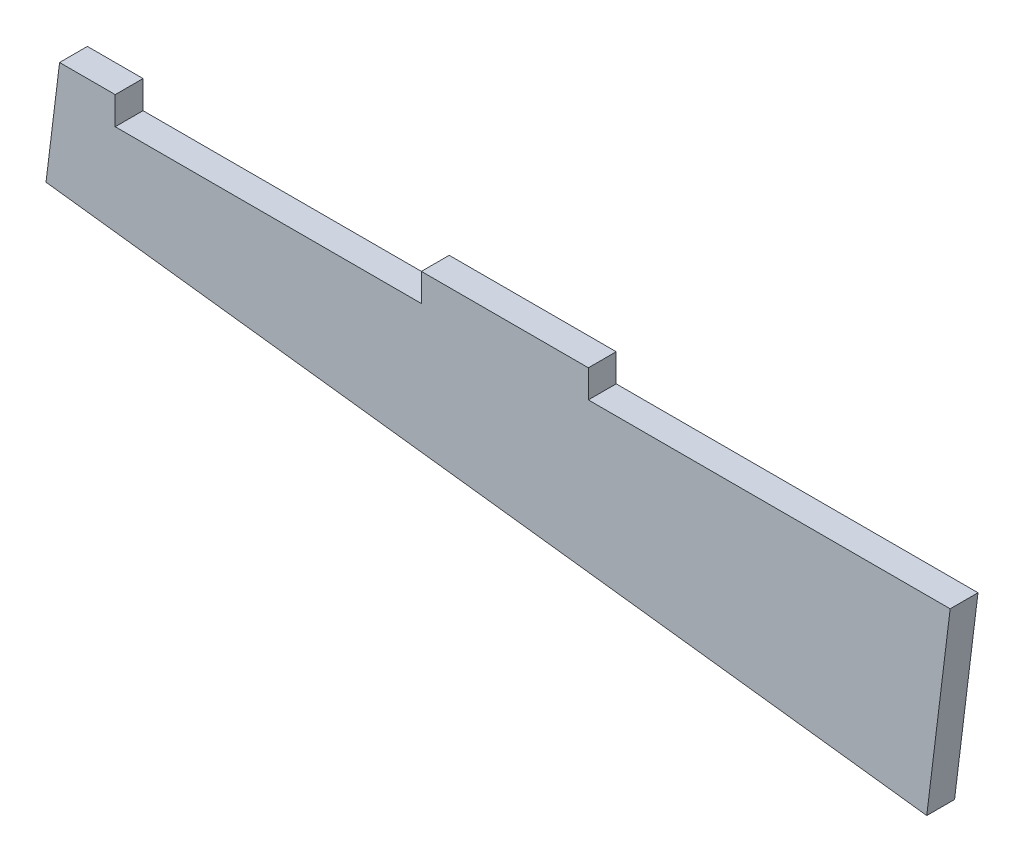
SolidWorks part; units mm, degrees
ref_plane "Front Plane" through (0, 0, 0) normal (0, 0, 1) x (1, 0, 0)
ref_plane "Top Plane" through (0, 0, 0) normal (0, 1, 0) x (1, 0, 0)
ref_plane "Right Plane" through (0, 0, 0) normal (1, 0, 0) x (0, 0, -1)
sketch "Sketch1" plane through (0, 0, 0) normal (0, 0, 1) x (1, 0, 0)
  line L0 (-195.3168, -62.6592) -> (-182.6168, -62.6592)
  line L4 (-182.6168, -62.6592) -> (-182.6168, -69.0092)
  line L5 (-182.6168, -69.0092) -> (-112.7668, -69.0092)
  line L6 (-112.7668, -69.0092) -> (-112.7668, -62.6592)
  line L7 (-112.7668, -62.6592) -> (-74.6668, -62.6592)
  line L8 (-74.6668, -62.6592) -> (-74.6668, -69.0092)
  line L9 (-74.6668, -69.0092) -> (7.8832, -69.0092)
  line L10 (7.8832, -69.0092) -> (2.5379, -112.5435)
  line L11 (2.5379, -112.5435) -> (-198.4122, -87.8699)
  line L12 (-198.4122, -87.8699) -> (-195.3168, -62.6592)
  line L13 (-1134.2002, 38.726) -> (-740.5002, -9.6143) construction
  point P2 (-62.7286, -30.0583)
  dimension "D1" = 12.7
  dimension "D2" = 6.35
  dimension "D3" = 69.85
  dimension "D4" = 38.1
  dimension "D5" = 82.55
  dimension "D6" = 25.4
extrude "Boss-Extrude1" add sketch "Sketch1" against normal blind 6.35
